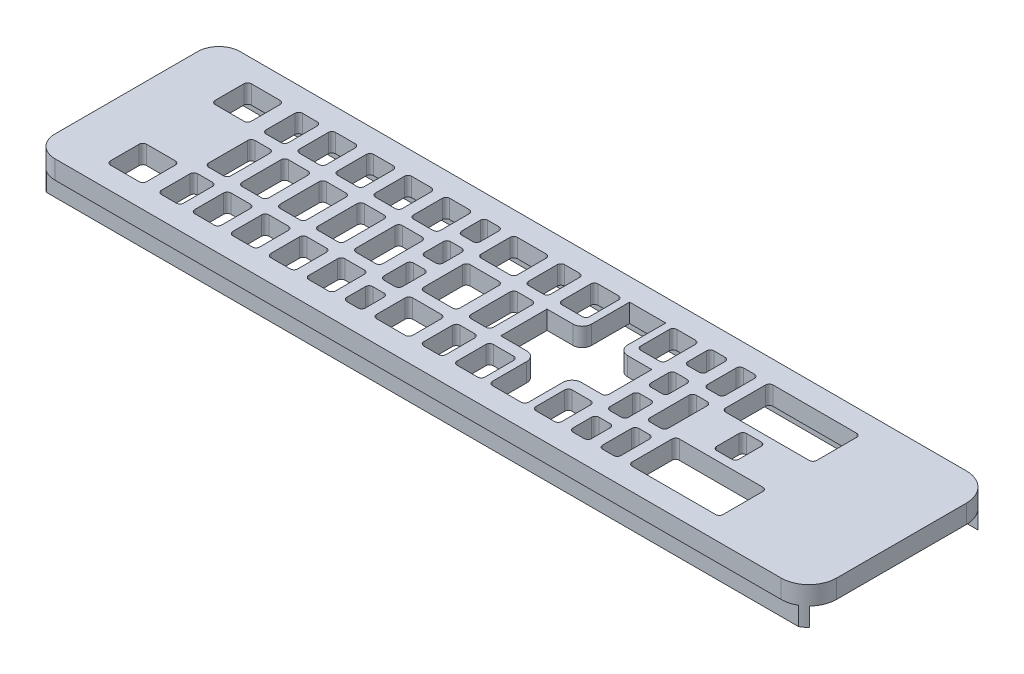
SolidWorks part; units mm, degrees
material "PVB"
ref_plane "Front Plane" through (0, 0, 0) normal (0, 0, 1) x (1, 0, 0)
ref_plane "Top Plane" through (0, 0, 0) normal (0, 1, 0) x (1, 0, 0)
ref_plane "Right Plane" through (0, 0, 0) normal (1, 0, 0) x (0, 0, -1)
ref_axis "X-axis" through (-88.99, 0, 0) along (1, 0, 0)
ref_axis "Y-axis" through (0, 55, 0) along (0, -1, 0)
ref_axis "Z-axis" through (0, 0, -88.99) along (0, 0, 1)
sketch "Sketch1" plane through (0, 0, 0) normal (0, 1, 0) x (1, 0, 0)
  line L1 (109.22, 25.4) -> (-109.22, 25.4)
  line L2 (109.22, 25.4) -> (109.22, -25.4)
  line L3 (109.22, -25.4) -> (-109.22, -25.4)
  line L4 (-109.22, 25.4) -> (-109.22, -25.4)
  line L5 (109.22, 25.4) -> (-109.22, -25.4) construction
  line L6 (109.22, -25.4) -> (-109.22, 25.4) construction
  point P0 (0, 0)
  point P6 (-109.22, -25.4)
  dimension "D1" = 218.44
  dimension "D2" = 50.8
extrude "Boss-Extrude1" add sketch "Sketch1" along normal blind 5.08
sketch "Sketch2" plane through (0, 0, 0) normal (0, -1, 0) x (1, 0, 0)
  line L0 (-109.22, 25.4) -> (109.22, 25.4) construction
  line L1 (108.204, 24.384) -> (-108.204, 24.384)
  line L2 (108.204, 24.384) -> (108.204, -24.384)
  line L3 (108.204, -24.384) -> (-108.204, -24.384)
  line L4 (-108.204, 24.384) -> (-108.204, -24.384)
  line L5 (108.204, 24.384) -> (-108.204, -24.384) construction
  line L6 (108.204, -24.384) -> (-108.204, 24.384) construction
  line L7 (-109.22, -25.4) -> (-109.22, 25.4) construction
  point P0 (0, 0)
  dimension "D1" = 1.016
  dimension "D2" = 1.016
extrude "Boss-Extrude2" add sketch "Sketch2" along normal blind 5.08
sketch "Sketch3" plane through (0, -5.08, 0) normal (0, -1, 0) x (1, 0, 0)
  line L0 (108.204, 24.384) -> (-108.204, 24.384) construction
  line L1 (106.934, 23.114) -> (-106.934, 23.114)
  line L2 (106.934, 23.114) -> (106.934, -23.114)
  line L3 (106.934, -23.114) -> (-106.934, -23.114)
  line L4 (-106.934, 23.114) -> (-106.934, -23.114)
  line L5 (106.934, 23.114) -> (-106.934, -23.114) construction
  line L6 (106.934, -23.114) -> (-106.934, 23.114) construction
  line L7 (-108.204, 24.384) -> (-108.204, -24.384) construction
  point P0 (0, 0)
  dimension "D1" = 1.27
  dimension "D2" = 1.27
extrude "Cut-Extrude1" cut sketch "Sketch3" against normal blind 5.08
fillet "Fillet1" radius 2.54 8 edges at (-109.22, 2.54, -25.4) (-108.204, -2.54, -24.384) (-109.22, 2.54, 25.4) (-108.204, -2.54, 24.384) (109.22, 2.54, 25.4) (109.22, 2.54, -25.4) (106.934, -2.54, -23.114) (108.204, -2.54, 24.384)
sketch "Sketch4" plane through (0, 5.08, 0) normal (0, 1, 0) x (1, 0, 0)
  line L0 (-94.234, 19.304) -> (-94.234, 9.398)
  line L1 (106.68, 25.4) -> (-106.68, 25.4) construction
  line L2 (-106.68, -25.4) -> (106.68, -25.4) construction
  line L3 (-109.22, 22.86) -> (-109.22, -22.86) construction
  line L4 (-84.328, 19.304) -> (-84.328, 9.398)
  line L5 (-80.264, 19.304) -> (-80.264, 9.398)
  line L6 (-74.168, 19.304) -> (-74.168, 9.398)
  line L7 (-71.12, 19.304) -> (-71.12, 9.398)
  line L8 (-63.754, 19.304) -> (-63.754, 9.398)
  line L9 (-60.706, 19.304) -> (-60.706, 9.398)
  line L10 (-53.34, 19.304) -> (-53.34, 9.398)
  line L11 (-50.292, 19.304) -> (-50.292, 9.398)
  line L12 (-42.926, 19.304) -> (-42.926, 9.398)
  line L13 (-39.878, 19.304) -> (-39.878, 9.398)
  line L14 (-32.512, 19.304) -> (-32.512, 9.398)
  line L15 (-29.464, 19.304) -> (-29.464, 12.192)
  line L16 (40.64, 19.304) -> (40.64, 9.398)
  line L17 (37.592, 19.304) -> (37.592, 12.192)
  line L18 (32.512, 19.304) -> (32.512, 12.192)
  line L19 (29.464, 19.304) -> (29.464, 9.398)
  line L20 (22.352, 19.304) -> (22.352, 9.398)
  line L21 (20.32, 19.304) -> (20.32, 6.35)
  line L22 (10.414, 19.304) -> (10.414, 6.35)
  line L23 (-24.384, 19.304) -> (-24.384, 12.192)
  line L24 (-21.336, 19.304) -> (-21.336, 9.398)
  line L25 (-11.43, 19.304) -> (-11.43, 8.8607)
  line L26 (-8.382, 19.304) -> (-8.382, -6.35)
  line L27 (-2.286, 19.304) -> (-2.286, -6.35)
  line L28 (0.762, 19.304) -> (0.762, 9.398)
  line L29 (8.382, 19.304) -> (8.382, 9.398)
  line L30 (-94.234, 19.304) -> (-84.328, 19.304)
  line L31 (-94.234, -19.304) -> (-84.328, -19.304)
  line L32 (-94.234, -9.398) -> (-84.328, -9.398)
  line L33 (-94.234, 9.398) -> (-84.328, 9.398)
  line L34 (-29.464, 9.144) -> (-24.384, 9.144)
  line L35 (-29.464, -9.144) -> (-24.384, -9.144)
  line L36 (-80.264, -19.304) -> (-74.168, -19.304)
  line L37 (-80.264, -9.398) -> (-74.168, -9.398)
  line L38 (-80.264, -6.35) -> (-74.168, -6.35)
  line L39 (-80.264, 9.398) -> (-74.168, 9.398)
  line L40 (-80.264, 6.35) -> (-74.168, 6.35)
  line L41 (-80.264, 19.304) -> (-74.168, 19.304)
  line L42 (-39.878, -19.304) -> (-32.512, -19.304)
  line L43 (-39.878, -9.398) -> (-32.512, -9.398)
  line L44 (-39.878, -6.35) -> (-32.512, -6.35)
  line L45 (-39.878, 6.35) -> (-32.512, 6.35)
  line L46 (-39.878, 9.398) -> (-32.512, 9.398)
  line L47 (-50.292, -19.304) -> (-42.926, -19.304)
  line L48 (-50.292, -9.398) -> (-42.926, -9.398)
  line L49 (-50.292, -6.35) -> (-42.926, -6.35)
  line L50 (-50.292, 6.35) -> (-42.926, 6.35)
  line L51 (-50.292, 9.398) -> (-42.926, 9.398)
  line L52 (-60.706, -19.304) -> (-53.34, -19.304)
  line L53 (-60.706, -9.398) -> (-53.34, -9.398)
  line L54 (-60.706, -6.35) -> (-53.34, -6.35)
  line L55 (-60.706, 6.35) -> (-53.34, 6.35)
  line L56 (-60.706, 9.398) -> (-53.34, 9.398)
  line L57 (-71.12, -19.304) -> (-63.754, -19.304)
  line L58 (-71.12, -9.398) -> (-63.754, -9.398)
  line L59 (-71.12, -6.35) -> (-63.754, -6.35)
  line L60 (-71.12, 6.35) -> (-63.754, 6.35)
  line L61 (-71.12, 9.398) -> (-63.754, 9.398)
  line L62 (-71.12, 19.304) -> (-63.754, 19.304)
  line L63 (-60.706, 19.304) -> (-53.34, 19.304)
  line L64 (-50.292, 19.304) -> (-42.926, 19.304)
  line L65 (-39.878, 19.304) -> (-32.512, 19.304)
  line L66 (-94.234, -9.398) -> (-94.234, -19.304)
  line L67 (-84.328, -9.398) -> (-84.328, -19.304)
  line L68 (-29.464, 12.192) -> (-24.384, 12.192)
  line L69 (-29.464, -1.016) -> (-24.384, -1.016)
  line L70 (-29.464, 2.032) -> (-24.384, 2.032)
  line L71 (-29.464, -12.192) -> (-24.384, -12.192)
  line L72 (-29.464, 19.304) -> (-24.384, 19.304)
  line L73 (-29.464, -19.304) -> (-24.384, -19.304)
  line L74 (-80.264, -9.398) -> (-80.264, -19.304)
  line L75 (-74.168, -9.398) -> (-74.168, -19.304)
  line L76 (-71.12, -9.398) -> (-71.12, -19.304)
  line L77 (-63.754, -9.398) -> (-63.754, -19.304)
  line L78 (-60.706, -9.398) -> (-60.706, -19.304)
  line L79 (-53.34, -9.398) -> (-53.34, -19.304)
  line L80 (-50.292, -9.398) -> (-50.292, -19.304)
  line L81 (-42.926, -9.398) -> (-42.926, -19.304)
  line L82 (-39.878, -9.398) -> (-39.878, -19.304)
  line L83 (-32.512, -9.398) -> (-32.512, -19.304)
  line L84 (-32.512, 6.35) -> (-32.512, -6.35)
  line L85 (-39.878, 6.35) -> (-39.878, -6.35)
  line L86 (-42.926, 6.35) -> (-42.926, -6.35)
  line L87 (-50.292, 6.35) -> (-50.292, -6.35)
  line L88 (-53.34, 6.35) -> (-53.34, -6.35)
  line L89 (-60.706, 6.35) -> (-60.706, -6.35)
  line L90 (-63.754, 6.35) -> (-63.754, -6.35)
  line L91 (-71.12, 6.35) -> (-71.12, -6.35)
  line L92 (-74.168, 6.35) -> (-74.168, -6.35)
  line L93 (-80.264, 6.35) -> (-80.264, -6.35)
  line L94 (-29.464, -12.192) -> (-29.464, -19.304)
  line L95 (-24.384, -12.192) -> (-24.384, -19.304)
  line L96 (-24.384, -1.016) -> (-24.384, -9.144)
  line L97 (-29.464, -1.016) -> (-29.464, -9.144)
  line L98 (-29.464, 9.144) -> (-29.464, 2.032)
  line L99 (-24.384, 9.144) -> (-24.384, 2.032)
  line L100 (-21.336, -19.304) -> (-11.43, -19.304)
  line L101 (-21.336, -9.398) -> (-11.43, -9.398)
  line L102 (-21.336, -6.35) -> (-11.43, -6.35)
  line L103 (-21.336, 6.35) -> (-11.43, 6.35)
  line L104 (-21.336, 9.398) -> (-11.43, 9.398)
  line L105 (-21.336, 19.304) -> (-11.43, 19.304)
  line L106 (-21.336, -9.398) -> (-21.336, -19.304)
  line L107 (-11.43, -9.398) -> (-11.43, -19.304)
  line L108 (-21.336, 6.35) -> (-21.336, -6.35)
  line L109 (-8.382, 19.304) -> (-2.286, 19.304)
  line L110 (-2.286, 19.304) -> (-2.286, 9.398)
  line L111 (-2.286, 9.398) -> (-8.382, 9.398)
  line L112 (-8.382, 9.398) -> (-8.382, 19.304)
  line L113 (-8.382, 6.35) -> (-2.286, 6.35)
  line L114 (-2.286, 6.35) -> (-2.286, -6.35)
  line L115 (-2.286, -6.35) -> (-8.382, -6.35)
  line L116 (-8.382, -6.35) -> (-8.382, 6.35)
  line L117 (-11.43, 6.35) -> (-11.43, -6.35)
  line L118 (-11.43, 9.398) -> (-11.43, 19.304)
  line L119 (-8.382, -9.398) -> (-2.286, -9.398)
  line L120 (-2.286, -9.398) -> (-2.286, -19.304)
  line L121 (-2.286, -19.304) -> (-8.382, -19.304)
  line L122 (-8.382, -19.304) -> (-8.382, -9.398)
  line L123 (0.762, -19.304) -> (8.382, -19.304)
  line L124 (8.382, -19.304) -> (8.382, -9.398)
  line L125 (8.382, -9.398) -> (0.762, -9.398)
  line L126 (0.762, -9.398) -> (0.762, -19.304)
  line L127 (0.762, 9.398) -> (8.382, 9.398)
  line L128 (8.382, 9.398) -> (8.382, 19.304)
  line L129 (8.382, 19.304) -> (0.762, 19.304)
  line L130 (0.762, 19.304) -> (0.762, 9.398)
  line L131 (0.762, 6.35) -> (8.382, 6.35)
  line L132 (0.762, 6.35) -> (0.762, -6.35)
  line L133 (0.762, -6.35) -> (8.382, -6.35)
  line L134 (10.414, -19.304) -> (20.32, -19.304)
  line L135 (20.32, -19.304) -> (20.32, -8.89)
  line L136 (22.86, -6.35) -> (29.464, -6.35)
  line L137 (29.464, -6.35) -> (29.464, 6.35)
  line L138 (29.464, 6.35) -> (22.86, 6.35)
  line L139 (20.32, 8.89) -> (20.32, 19.304)
  line L140 (20.32, 19.304) -> (10.414, 19.304)
  line L141 (10.414, 19.304) -> (10.414, 6.35)
  line L142 (10.414, 6.35) -> (8.382, 6.35)
  line L143 (10.414, -19.304) -> (10.414, -6.35)
  line L144 (10.414, -6.35) -> (8.382, -6.35)
  line L145 (22.352, -19.304) -> (29.464, -19.304)
  line L146 (29.464, -19.304) -> (29.464, -9.398)
  line L147 (29.464, -9.398) -> (22.352, -9.398)
  line L148 (22.352, -9.398) -> (22.352, -19.304)
  line L149 (22.352, 9.398) -> (29.464, 9.398)
  line L150 (29.464, 9.398) -> (29.464, 19.304)
  line L151 (29.464, 19.304) -> (22.352, 19.304)
  line L152 (22.352, 19.304) -> (22.352, 9.398)
  line L153 (45.6438, 19.304) -> (45.6438, 9.398)
  line L154 (48.6918, 19.304) -> (48.6918, 6.35)
  line L155 (40.64, -19.304) -> (45.6438, -19.304)
  line L156 (45.6438, -19.304) -> (45.6438, -9.398)
  line L157 (45.6438, -9.398) -> (40.64, -9.398)
  line L158 (40.64, -9.398) -> (40.64, -19.304)
  line L159 (40.64, -6.35) -> (45.6438, -6.35)
  line L160 (45.6438, -6.35) -> (45.6438, 6.35)
  line L161 (45.6438, 6.35) -> (40.64, 6.35)
  line L162 (40.64, 6.35) -> (40.64, -6.35)
  line L163 (40.64, 19.304) -> (45.6438, 19.304)
  line L164 (45.6438, 19.304) -> (45.6438, 9.398)
  line L165 (45.6438, 9.398) -> (40.64, 9.398)
  line L166 (40.64, 9.398) -> (40.64, 19.304)
  line L167 (32.512, -12.192) -> (37.592, -12.192)
  line L168 (37.592, -12.192) -> (37.592, -19.304)
  line L169 (37.592, -19.304) -> (32.512, -19.304)
  line L170 (32.512, -19.304) -> (32.512, -12.192)
  line L171 (32.512, -9.144) -> (37.592, -9.144)
  line L172 (37.592, -9.144) -> (37.592, -1.016)
  line L173 (37.592, -1.016) -> (32.512, -1.016)
  line L174 (32.512, -1.016) -> (32.512, -9.144)
  line L175 (32.512, 2.032) -> (37.592, 2.032)
  line L176 (37.592, 2.032) -> (37.592, 8.8607)
  line L177 (37.592, 8.8607) -> (32.512, 8.8607)
  line L178 (32.512, 8.8607) -> (32.512, 2.032)
  line L179 (32.512, 12.192) -> (37.592, 12.192)
  line L180 (37.592, 12.192) -> (37.592, 19.304)
  line L181 (37.592, 19.304) -> (32.512, 19.304)
  line L182 (32.512, 19.304) -> (32.512, 12.192)
  line L183 (10.414, -6.35) -> (10.414, -19.304)
  line L184 (8.382, -9.398) -> (8.382, -19.304)
  line L185 (20.32, -6.35) -> (20.32, -19.304)
  line L186 (22.352, -9.398) -> (22.352, -19.304)
  line L187 (0.762, -9.398) -> (0.762, -19.304)
  line L188 (-2.286, -9.398) -> (-2.286, -19.304)
  line L189 (-8.382, -9.398) -> (-8.382, -19.304)
  line L190 (0.762, 6.35) -> (0.762, -6.35)
  line L191 (29.464, 6.35) -> (29.464, -6.35)
  line L192 (29.464, -9.398) -> (29.464, -19.304)
  line L193 (32.512, 8.8607) -> (32.512, 2.032)
  line L194 (37.592, 8.8607) -> (37.592, 2.032)
  line L195 (32.512, -1.016) -> (32.512, -9.144)
  line L196 (37.592, -1.016) -> (37.592, -9.144)
  line L197 (32.512, -12.192) -> (32.512, -19.304)
  line L198 (37.592, -12.192) -> (37.592, -19.304)
  line L199 (40.64, -9.398) -> (40.64, -19.304)
  line L200 (45.6438, -9.398) -> (45.6438, -19.304)
  line L201 (40.64, 6.35) -> (40.64, -6.35)
  line L202 (45.6438, 6.35) -> (45.6438, -6.35)
  line L203 (48.6918, -19.304) -> (73.6092, -19.304)
  line L205 (48.6918, 19.304) -> (73.6092, 19.304)
  line L206 (73.6092, 6.35) -> (48.6918, 6.35)
  line L207 (48.6918, -6.35) -> (73.6092, -6.35)
  line L208 (56.5658, -3.9841) -> (62.6618, -3.9841)
  line L209 (56.5658, 4.1578) -> (62.6618, 4.1578)
  line L212 (73.6092, 19.304) -> (73.6092, 6.35)
  line L215 (62.6618, 4.1578) -> (62.6618, -3.9841)
  line L216 (56.5658, 4.1578) -> (56.5658, -3.9841)
  line L217 (48.6918, -6.35) -> (48.6918, -19.304)
  line L220 (73.6092, -6.35) -> (73.6092, -19.304)
  arc A0 (22.86, 6.35) -> (20.32, 8.89) centre (22.86, 8.89) cw
  arc A1 (20.32, -8.89) -> (22.86, -6.35) centre (22.86, -8.89) cw
  point P39 (56.5658, 0.0869)
  dimension "D40" = 2.54
  dimension "D41" = 2.54
  dimension "D1" = 14.986
  dimension "D2" = 9.906
  dimension "D3" = 4.064
  dimension "D4" = 6.096
  dimension "D5" = 3.048
  dimension "D6" = 7.366
  dimension "D7" = 3.048
  dimension "D8" = 7.366
  dimension "D9" = 3.048
  dimension "D10" = 7.366
  dimension "D11" = 3.048
  dimension "D12" = 7.366
  dimension "D13" = 3.048
  dimension "D14" = 5.08
  dimension "D15" = 3.048
  dimension "D16" = 9.906
  dimension "D17" = 3.048
  dimension "D18" = 6.096
  dimension "D19" = 3.048
  dimension "D20" = 7.62
  dimension "D21" = 6.096
  dimension "D22" = 6.096
  dimension "D23" = 9.906
  dimension "D24" = 9.906
  dimension "D25" = 7.112
  dimension "D26" = 3.048
  dimension "D27" = 7.112
  dimension "D28" = 3.048
  dimension "D29" = 7.112
  dimension "D30" = 3.048
  dimension "D31" = 2.032
  dimension "D32" = 9.906
  dimension "D33" = 2.032
  dimension "D34" = 7.112
  dimension "D35" = 3.048
  dimension "D36" = 5.08
  dimension "D37" = 3.048
  dimension "D38" = 3.048
  dimension "D39" = 5.0038
  dimension "D42" = 12.954
  dimension "D43" = 12.954
  dimension "D44" = 10.922
  dimension "D46" = 24.9174
extrude "Cut-Extrude2" cut sketch "Sketch4" against normal through all contours L67 L32 L66 L31 | L0 L33 L4 L30 | L6 L39 L5 L41 | L38 L92 L40 L93 | L36 L75 L37 L74 | L57 L77 L58 L76 | L59 L90 L60 L91 | L8 L61 L7 L62 | L10 L56 L9 L63 | L54 L88 L55 L89 | L52 L79 L53 L78 | L49 L86 L50 L87 | L12 L51 L11 L64 | L47 L81 L48 L80 | L42 L83 L43 L82 | L44 L84 L45 L85 | L14 L46 L13 L65 | L15 L68 L23 L72 | L70 L99 L34 L98 | L35 L96 L69 L97 | L71 L95 L73 L94 | L105 L24 L104 L118 | L112 L109 L110 L111 | L117 L102 L108 L103 | L116 L113 L114 L115 | L100 L107 L101 L106 | L122 L119 L120 L121 | L126 L123 L124 L125 | L144 L133 L132 L131 L142 L141 L140 L139 A0 L138 L137 L136 A1 L135 L134 L143 | L130 L127 L128 L129 | L152 L149 L150 L151 | L182 L179 L180 L181 | L166 L163 L164 L165 | L162 L159 L160 L161 | L174 L171 L172 L173 | L178 L175 L176 L177 | L148 L145 L146 L147 | L170 L167 L168 L169 | L158 L155 L156 L157 | L203 L220 L207 L217 | L216 L208 L215 L209 | L212 L206 L154 L205 region at (-89.281, 5.08, 14.351)
fillet "Fillet2" radius 2.54 2 edges at (10.414, 2.54, -6.35) (10.414, 2.54, 6.35)
fillet "Fillet3" radius 1.016 12 edges at (56.5658, 2.54, -4.1578) (56.5658, 2.54, 3.9841) (62.6618, 2.54, -4.1578) (62.6618, 2.54, 3.9841) (73.6092, 2.54, 19.304) (73.6092, 2.54, -6.35) (73.6092, 2.54, -19.304) (73.6092, 2.54, 6.35) (48.6918, 2.54, 6.35) (48.6918, 2.54, 19.304) (48.6918, 2.54, -6.35) (48.6918, 2.54, -19.304)
fillet "Fillet4" radius 1.016 40 edges at (-84.328, 2.54, -9.398) (-74.168, 2.54, -9.398) (-74.168, 2.54, 6.35) (-74.168, 2.54, 19.304) (-84.328, 2.54, 19.304) (-63.754, 2.54, -9.398) (-63.754, 2.54, 6.35) (-63.754, 2.54, 19.304) (-53.34, 2.54, 19.304) (-53.34, 2.54, 6.35) (-53.34, 2.54, -9.398) (-42.926, 2.54, -9.398) (-42.926, 2.54, 6.35) (-42.926, 2.54, 19.304) (-32.512, 2.54, 19.304) (-32.512, 2.54, 6.35) (-32.512, 2.54, -9.398) (-24.384, 2.54, -12.192) (-24.384, 2.54, -2.032) (-24.384, 2.54, 9.144) (-24.384, 2.54, 19.304) (20.32, 2.54, 19.304) (-11.43, 2.54, 19.304) (-11.43, 2.54, 6.35) (-11.43, 2.54, -9.398) (-2.286, 2.54, -9.398) (-2.286, 2.54, 6.35) (-2.286, 2.54, 19.304) (8.382, 2.54, 19.304) (8.382, 2.54, -9.398) (29.464, 2.54, -9.398) (29.464, 2.54, 6.35) (29.464, 2.54, 19.304) (37.592, 2.54, 19.304) (37.592, 2.54, 9.144) (37.592, 2.54, -2.032) (37.592, 2.54, -12.192) (45.6438, 2.54, -9.398) (45.6438, 2.54, 6.35) (45.6438, 2.54, 19.304)
fillet "Fillet5" radius 1.016 38 edges at (29.464, 2.54, -19.304) (37.592, 2.54, -8.8607) (37.592, 2.54, -19.304) (45.6438, 2.54, -19.304) (45.6438, 2.54, -6.35) (45.6438, 2.54, 9.398) (37.592, 2.54, 1.016) (37.592, 2.54, 12.192) (29.464, 2.54, 9.398) (8.382, 2.54, 9.398) (8.382, 2.54, -19.304) (-2.286, 2.54, -19.304) (-2.286, 2.54, -6.35) (-2.286, 2.54, 9.398) (-11.43, 2.54, 9.398) (-11.43, 2.54, -6.35) (-11.43, 2.54, -19.304) (-24.384, 2.54, -19.304) (-24.384, 2.54, -9.144) (-24.384, 2.54, 1.016) (-24.384, 2.54, 12.192) (-32.512, 2.54, 9.398) (-32.512, 2.54, -6.35) (-32.512, 2.54, -19.304) (-42.926, 2.54, -19.304) (-42.926, 2.54, -6.35) (-42.926, 2.54, 9.398) (-53.34, 2.54, -19.304) (-53.34, 2.54, -6.35) (-53.34, 2.54, 9.398) (-63.754, 2.54, -19.304) (-63.754, 2.54, -6.35) (-63.754, 2.54, 9.398) (-74.168, 2.54, 9.398) (-74.168, 2.54, -6.35) (-74.168, 2.54, -19.304) (-84.328, 2.54, -19.304) (-84.328, 2.54, 9.398)
fillet "Fillet6" radius 1.016 39 edges at (-71.12, 2.54, -9.398) (-71.12, 2.54, 6.35) (-80.264, 2.54, 6.35) (-80.264, 2.54, -9.398) (-94.234, 2.54, -9.398) (-94.234, 2.54, 19.304) (-80.264, 2.54, 19.304) (-60.706, 2.54, 19.304) (-71.12, 2.54, 19.304) (-60.706, 2.54, 6.35) (-60.706, 2.54, -9.398) (-50.292, 2.54, 19.304) (-50.292, 2.54, 6.35) (-50.292, 2.54, -9.398) (-39.878, 2.54, -9.398) (-39.878, 2.54, 6.35) (-39.878, 2.54, 19.304) (0.762, 2.54, -9.398) (-8.382, 2.54, -9.398) (-8.382, 2.54, 6.35) (-21.336, 2.54, 6.35) (-21.336, 2.54, -9.398) (-29.464, 2.54, -12.192) (-29.464, 2.54, -2.032) (-29.464, 2.54, 9.144) (-29.464, 2.54, 19.304) (-21.336, 2.54, 19.304) (-8.382, 2.54, 19.304) (0.762, 2.54, 19.304) (10.414, 2.54, 19.304) (22.352, 2.54, -9.398) (22.352, 2.54, 19.304) (32.512, 2.54, 19.304) (32.512, 2.54, 9.144) (32.512, 2.54, -2.032) (32.512, 2.54, -12.192) (40.64, 2.54, -9.398) (40.64, 2.54, 6.35) (40.64, 2.54, 19.304)
fillet "Fillet7" radius 1.016 38 edges at (40.64, 2.54, -6.35) (40.64, 2.54, -19.304) (32.512, 2.54, -19.304) (32.512, 2.54, -8.8607) (32.512, 2.54, 1.016) (32.512, 2.54, 12.192) (40.64, 2.54, 9.398) (22.352, 2.54, -19.304) (22.352, 2.54, 9.398) (0.762, 2.54, 9.398) (0.762, 2.54, -19.304) (-8.382, 2.54, -19.304) (-8.382, 2.54, 9.398) (-8.382, 2.54, -6.35) (-21.336, 2.54, -19.304) (-21.336, 2.54, -6.35) (-21.336, 2.54, 9.398) (-29.464, 2.54, 12.192) (-29.464, 2.54, 1.016) (-29.464, 2.54, -9.144) (-29.464, 2.54, -19.304) (-39.878, 2.54, -19.304) (-39.878, 2.54, -6.35) (-39.878, 2.54, 9.398) (-50.292, 2.54, 9.398) (-50.292, 2.54, -6.35) (-50.292, 2.54, -19.304) (-60.706, 2.54, -19.304) (-60.706, 2.54, -6.35) (-60.706, 2.54, 9.398) (-71.12, 2.54, 9.398) (-71.12, 2.54, -19.304) (-71.12, 2.54, -6.35) (-80.264, 2.54, -19.304) (-94.234, 2.54, -19.304) (-80.264, 2.54, -6.35) (-80.264, 2.54, 9.398) (-94.234, 2.54, 9.398)
fillet "Fillet8" radius 2.54 4 edges at (-106.934, -2.54, -23.114) (-106.934, -2.54, 23.114) (106.934, -2.54, 23.114) (108.204, -2.54, -24.384)
sketch "Sketch6" plane through (0, 0, 0) normal (0, 1, 0) x (1, 0, 0)
  line L0 (106.68, 25.4) -> (-105.555, 25.4) construction
  line L1 (104.2474, 25.4) -> (109.6895, 25.4)
  line L2 (104.2474, 25.4) -> (104.2474, -25.4)
  line L3 (104.2474, -25.4) -> (109.6895, -25.4)
  line L4 (109.6895, 25.4) -> (109.6895, -25.4)
  line L5 (-105.555, -25.4) -> (106.68, -25.4) construction
  point P6 (111.5437, -25.5188)
  point P7 (103.9783, -25.4)
  point P10 (0, 0)
  point P11 (0, 0)
  point P12 (0, 0)
  point P13 (114.0926, -25.4)
  point P14 (102.5125, -25.4)
  point P15 (104.2474, -25.4)
  point P16 (109.6895, -25.4)
extrude "Cut-Extrude7" cut sketch "Sketch6" against normal through all both and the other way through all contours L4 L3 L2 L1
fillet "Fillet11" radius 7.62 2 edges at (104.2474, 2.54, -25.4) (104.2474, 2.54, 25.4)
sketch "Sketch7" plane through (0, 0, 0) normal (0, 0, 1) x (1, 0, 0)
  line L0 (-108.204, -5.08) -> (-105.664, -5.08) construction
  line L1 (-109.22, 5.08) -> (-108.204, 5.08)
  line L2 (-109.22, 5.08) -> (-109.22, -5.08)
  line L3 (-109.22, -5.08) -> (-108.204, -5.08)
  line L4 (-108.204, 5.08) -> (-108.204, -5.08)
  line L5 (-108.204, -5.08) -> (-108.204, 0) construction
  point P5 (-108.4144, -5.0723)
  point P6 (-108.1018, -5.08)
  point P9 (-108.2372, -5.08)
  point P10 (-108.1645, -5.08)
  point P11 (-108.2754, -5.08)
  point P12 (-108.204, -5.08)
extrude "Cut-Extrude8" cut sketch "Sketch7" against normal through all both and the other way through all
fillet "Fillet16" radius 5.842 2 edges at (-108.204, 2.54, -24.892) (-108.204, 2.54, 24.892)
